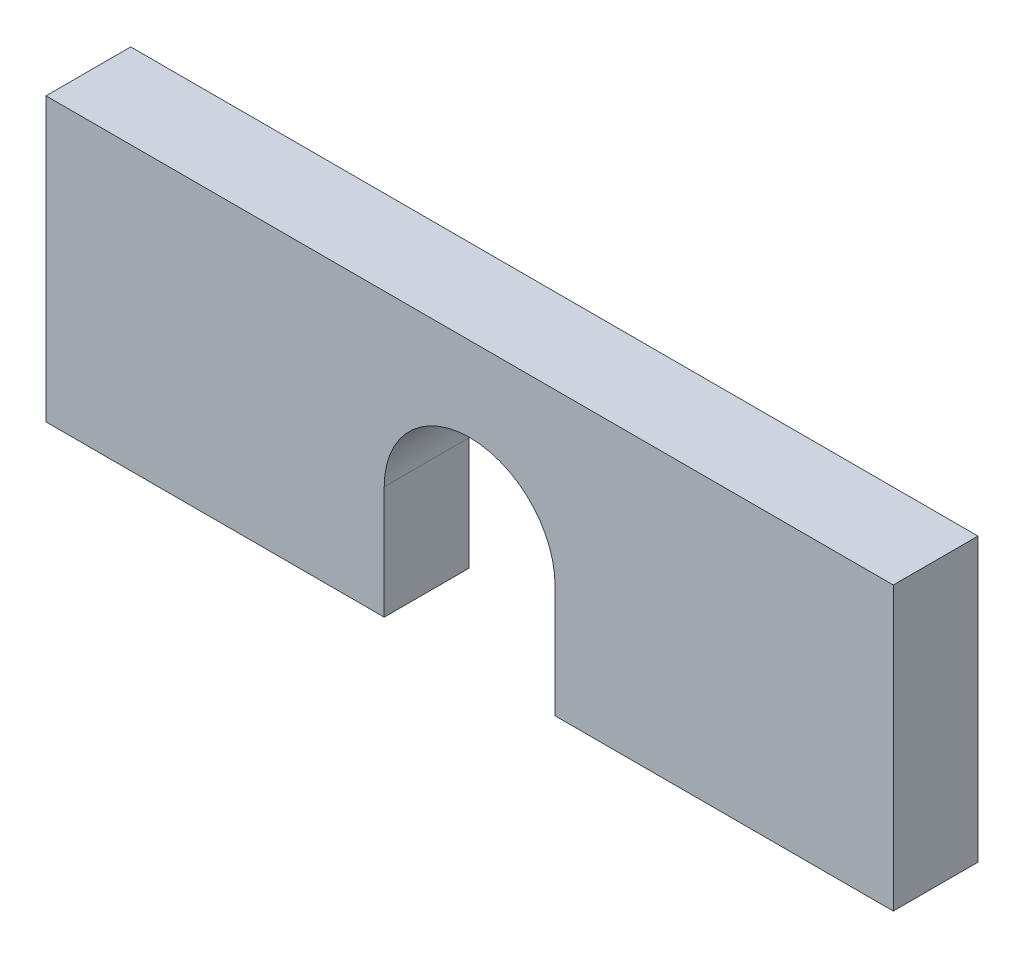
SolidWorks part; units mm, degrees
material "Клен"
ref_plane "Спереди" through (0, 0, 0) normal (0, 0, 1) x (1, 0, 0)
ref_plane "Сверху" through (0, 0, 0) normal (0, 1, 0) x (1, 0, 0)
ref_plane "Справа" through (0, 0, 0) normal (1, 0, 0) x (0, 0, -1)
sketch "Эскиз1" plane through (0, 0, 0) normal (0, 0, 1) x (1, 0, 0)
  line L0 (4.6404, 19.3784) -> (4.6404, 41.1477) construction
  line L1 (-25.9796, 11.0784) -> (34.0204, 11.0784)
  line L2 (-25.9796, 11.0784) -> (-25.9796, 31.0784)
  line L3 (-25.9796, 31.0784) -> (34.0204, 31.0784)
  line L4 (34.0204, 11.0784) -> (34.0204, 31.0784)
  line L7 (4.6404, 41.1477) -> (4.6404, -3.6034) construction
  dimension "D1" = 20
extrude "Бобышка-Вытянуть1" add sketch "Эскиз1" along normal blind 6 contours L2 L3 L4 L1
sketch "Эскиз2" plane through (0, 0, 6) normal (0, 0, 1) x (1, 0, 0)
  line L0 (4.0204, 33.3668) -> (4.0204, 11.0784) construction
  line L2 (4.0204, 11.0784) -> (4.0204, 19.0784) construction
  line L3 (-2.0296, 11.0784) -> (-2.0296, 19.0784)
  line L4 (10.0704, 11.0784) -> (10.0704, 19.0784)
  line L6 (-25.9796, 11.0784) -> (34.0204, 11.0784) construction
  line L7 (34.0204, 21.0784) -> (-25.9796, 21.0784) construction
  line L8 (34.0204, 11.0784) -> (34.0204, 31.0784) construction
  line L9 (-25.9796, 11.0784) -> (-25.9796, 31.0784) construction
  arc A1 (-2.0296, 11.0784) -> (10.0704, 11.0784) centre (4.0204, 11.0784) ccw
  arc A2 (10.0704, 19.0784) -> (-2.0296, 19.0784) centre (4.0204, 19.0784) ccw
  point P0 (4.0204, 15.0784)
  point P10 (4.0204, 11.0784)
  dimension "D1" = 12.1
  dimension "D2" = 8
extrude "Вырез-Вытянуть1" cut sketch "Эскиз2" against normal through all
ref_plane "Плоскость1" through (4.0204, 0, 0) normal (1, 0, 0) x (0, 0, -1)
